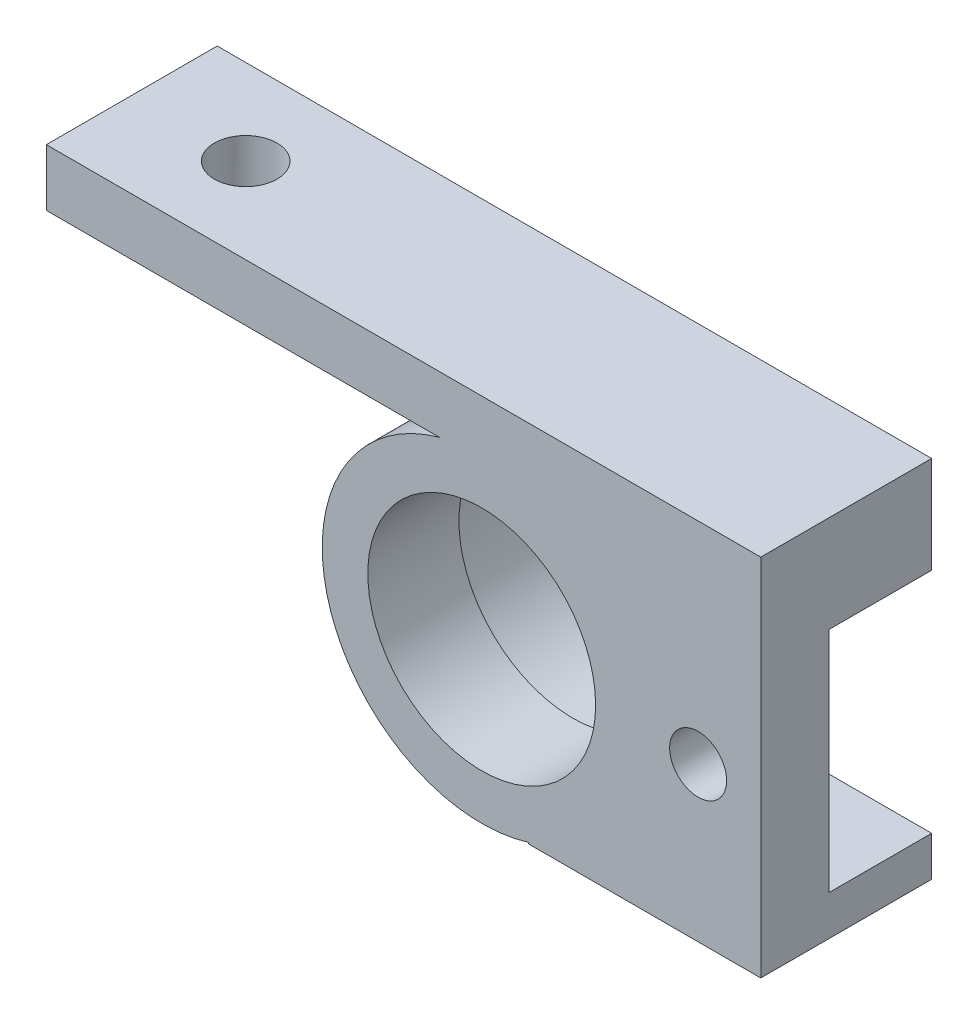
SolidWorks part; units mm, degrees
ref_plane "前视基准面" through (0, 0, 0) normal (0, 0, 1) x (1, 0, 0)
ref_plane "上视基准面" through (0, 0, 0) normal (0, 1, 0) x (1, 0, 0)
ref_plane "右视基准面" through (0, 0, 0) normal (1, 0, 0) x (0, 0, -1)
sketch "草图1" plane through (0, 0, 0) normal (0, 0, 1) x (1, 0, 0)
  line L1 (20, -10) -> (-20, -10)
  line L2 (20, -10) -> (20, 10)
  line L3 (20, 10) -> (-20, 10)
  line L4 (-20, -10) -> (-20, 10)
  line L5 (20, -10) -> (-20, 10) construction
  line L6 (20, 10) -> (-20, -10) construction
  point P0 (0, 0)
  dimension "D1" = 40
  dimension "D2" = 20
extrude "凸台-拉伸1" add sketch "草图1" along normal blind 6
sketch "草图2" plane through (0, 0, 6) normal (0, 0, 1) x (1, 0, 0)
  line L0 (20, -10) -> (20, 10) construction
  circle A0 centre (10, 0) radius 2.5
  circle A1 centre (-1, 0) radius 2.5
  circle A2 centre (-12, 0) radius 2.5
  dimension "D1" = 10
  dimension "D2" = 5
  dimension "D3" = 3
extrude "切除-拉伸1" cut sketch "草图2" against normal through all
sketch "草图3" plane through (0, 0, 6) normal (0, 0, 1) x (1, 0, 0)
  line L0 (20, 13.5) -> (20, 10)
  line L1 (20, -13.5) -> (-26.894, -13.5)
  line L3 (20, 13.5) -> (-26.894, 13.5)
  line L4 (-20, 10) -> (-20, -10)
  line L5 (-20, -10) -> (20, -10)
  line L6 (20, -10) -> (20, 10)
  line L7 (20, 10) -> (-20, 10)
  line L8 (-20, 10) -> (-20, -10)
  line L9 (-20, -10) -> (20, -10)
  line L10 (20, -10) -> (20, 10)
  line L11 (20, 10) -> (-20, 10)
  line L12 (-26.894, -13.5) -> (-26.894, 13.5)
  line L13 (20, -10.0394) -> (-26.894, 13.5) construction
  line L14 (20, 10.0394) -> (-26.894, -13.5) construction
  line L15 (20, -10) -> (20, -13.5)
  circle A0 centre (-31, 0) radius 11
  circle A1 centre (-31, 0) radius 14
  point P2 (0, 0)
  line M10 (-20, 10) -> (-20, -10)
  line M11 (-20, -10) -> (20, -10)
  line M13 (20, 10) -> (-20, 10)
  dimension "D3" = 22
  dimension "D4" = 28
  dimension "D2" = 3.5
  dimension "D1" = 0
extrude "凸台-拉伸2" add sketch "草图3" against normal blind 15 contours L3 A1 L1 L12 A0 | A1 L1 L15 M11 M10 | L1 A1 L8 A0 L12 | L8 A1 L3 L12 A0 | L8 A1 | A1 L0 L3 M10 M13 region at (-1.9449, 11.7771, 6) region at (-1.9449, -11.7771, 6) region at (-23.0173, 9.0328, 6) region at (-27.2274, 11.7946, 6) region at (-18.7882, 0, 6) region at (-23.0173, -9.0328, 6)
sketch "草图5" plane through (0, 0, 6) normal (0, 0, 1) x (1, 0, 0)
  circle A0 centre (-31, 0) radius 10
  circle A1 centre (-31, 0) radius 11 construction
  circle A2 centre (-31, 0) radius 11
  dimension "D1" = 20
extrude "凸台-拉伸3" add sketch "草图5" against normal blind 8
sketch "草图6" plane through (0, 0, 6) normal (0, 0, 1) x (1, 0, 0)
  circle A0 centre (-31, 0) radius 8.5
  circle A1 centre (-31, 0) radius 10 construction
  circle A2 centre (-31, 0) radius 10
  dimension "D1" = 17
sketch "草图7" plane through (0, 13.5, 0) normal (0, 1, 0) x (1, 0, 0)
  circle A0 centre (-17.1666, 1.953) radius 2.6594
sketch "草图8" plane through (20, 0, 0) normal (1, 0, 0) x (0, 0, -1)
  line L1 (-6, 13.5) -> (9, 13.5)
  line L2 (-6, 13.5) -> (-6, 18.5)
  line L3 (-6, 18.5) -> (9, 18.5)
  line L4 (9, 13.5) -> (9, 18.5)
  dimension "D1" = 5
extrude "凸台-拉伸4" add sketch "草图8" against normal blind 500
sketch "草图9" plane through (0, 0, -9) normal (0, 0, -1) x (-1, 0, 0)
  line L1 (24.4567, 15.8334) -> (28.494, 15.8334)
  line L2 (24.4567, 15.8334) -> (24.4567, 12.469)
  line L3 (24.4567, 12.469) -> (28.494, 12.469)
  line L4 (28.494, 15.8334) -> (28.494, 12.469)
extrude "凸台-拉伸5" add sketch "草图9" against normal through all
sketch "草图10" plane through (0, 0, 6) normal (0, 0, 1) x (1, 0, 0)
  line L0 (-12, 0) -> (-1, 0) construction
  line L1 (-6.5, 0) -> (-6.5, 18.5) construction
  line L2 (-480, 18.5) -> (20, 18.5) construction
  line L4 (-6.5, 18.5) -> (20, 18.5)
  line L5 (-6.5, 18.5) -> (-6.5, -13.5)
  line L6 (-6.5, -13.5) -> (20, -13.5)
  line L7 (20, 18.5) -> (20, -13.5)
extrude "切除-拉伸2" cut sketch "草图10" against normal through all
sketch "草图11" plane through (0, 18.5, 0) normal (0, 1, 0) x (1, 0, 0)
  line L0 (-69.2198, 9) -> (-69.2198, -6.0139)
  line L1 (-480, 9) -> (-6.5, 9) construction
  line L2 (-69.2198, 251.4142) -> (-69.2198, -118.5858) construction
sketch "草图12" plane through (0, 18.5, 0) normal (0, 1, 0) x (1, 0, 0)
  line L1 (-69.2198, -6.0139) -> (-501.7351, -6.0139)
  line L2 (-69.2198, -6.0139) -> (-69.2198, 21.5219)
  line L3 (-69.2198, 21.5219) -> (-501.7351, 21.5219)
  line L4 (-501.7351, -6.0139) -> (-501.7351, 21.5219)
extrude "切除-拉伸3" cut sketch "草图12" against normal through all
sketch "草图13" plane through (0, 18.5, 0) normal (0, 1, 0) x (1, 0, 0)
  line L0 (-59.2198, 9) -> (-59.2198, -6)
  line L1 (-69.2198, 9) -> (-6.5, 9) construction
  line L2 (-69.2198, -6) -> (-6.5, -6) construction
  line L3 (-69.2198, 9) -> (-69.2198, -6.0139) construction
  circle A0 centre (-59.2198, 1.5) radius 2.75
  dimension "D2" = 5.5
  dimension "D1" = 10
extrude "切除-拉伸4" cut sketch "草图13" against normal blind 10 contours A0
